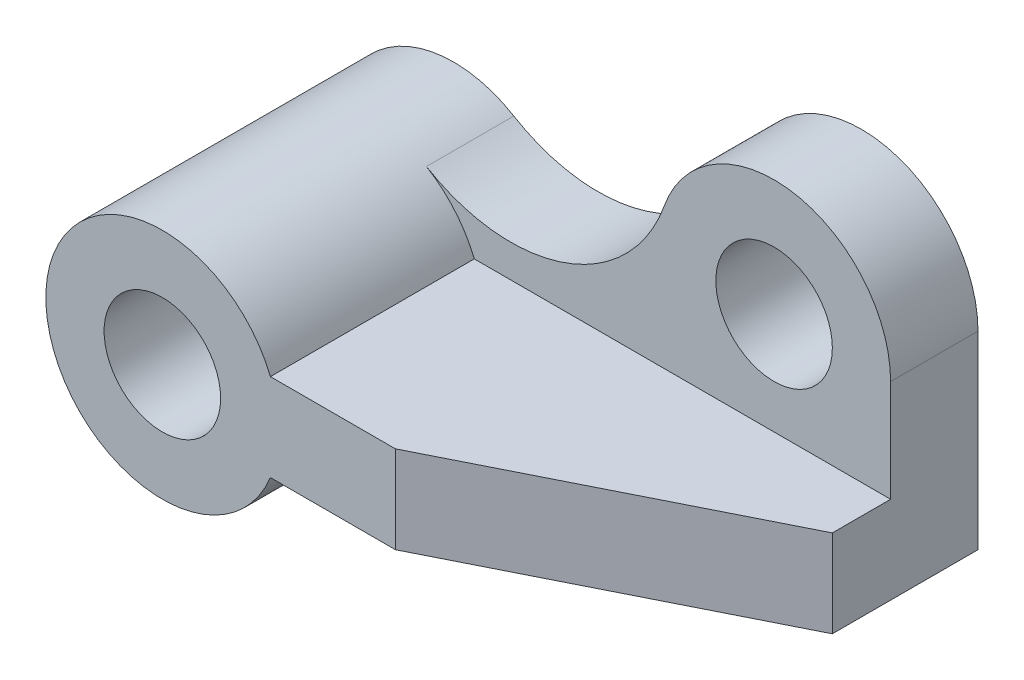
SolidWorks part; units mm, degrees
ref_plane "Front Plane" through (0, 0, 0) normal (0, 0, 1) x (1, 0, 0)
ref_plane "Top Plane" through (0, 0, 0) normal (0, 1, 0) x (1, 0, 0)
ref_plane "Right Plane" through (0, 0, 0) normal (1, 0, 0) x (0, 0, -1)
sketch "Sketch3" plane through (0, 0, 0) normal (0, 0, 1) x (1, 0, 0)
  line L0 (90, 25) -> (90, -7.5)
  line L1 (18.5405, 7.5) -> (90, 7.5)
  line L3 (18.5405, -7.5) -> (90, -7.5)
  line L4 (90, 7.5) -> (90, -7.5)
  arc A0 (18.5405, 7.5) -> (18.5405, -7.5) centre (0, 0) ccw
  circle A1 centre (0, 0) radius 10
  circle A2 centre (70, 25) radius 10
  arc A3 (90, 25) -> (51.1597, 31.7113) centre (70, 25) ccw
  arc A4 (10.3263, 17.128) -> (51.1597, 31.7113) centre (24.7832, 41.1071) ccw
  dimension "D7" = 40
  dimension "D8" = 20
  dimension "D9" = 28
  dimension "D3" = 15
  dimension "D4" = 7.5
  dimension "D5" = 90
  dimension "D6" = 25
extrude "Boss-Extrude2" add sketch "Sketch3" along normal blind 50 contours L1 A0 L3 L0 A1 region at (28.9502, 0, 0)
extrude "Boss-Extrude3" add sketch "Sketch3<4>" along normal blind 15 contours A4 A0 L1 L0 A3 A2 region at (89.1194, 16.25, 0)
sketch "Sketch3<4>" plane through (0, 0, 0) normal (0, 0, 1) x (1, 0, 0) same geometry as "Sketch3"
chamfer "Chamfer1" distance 50 distance2 25 1 edges at (90, 0, 50) first distance on face at (10, 0, 50)
